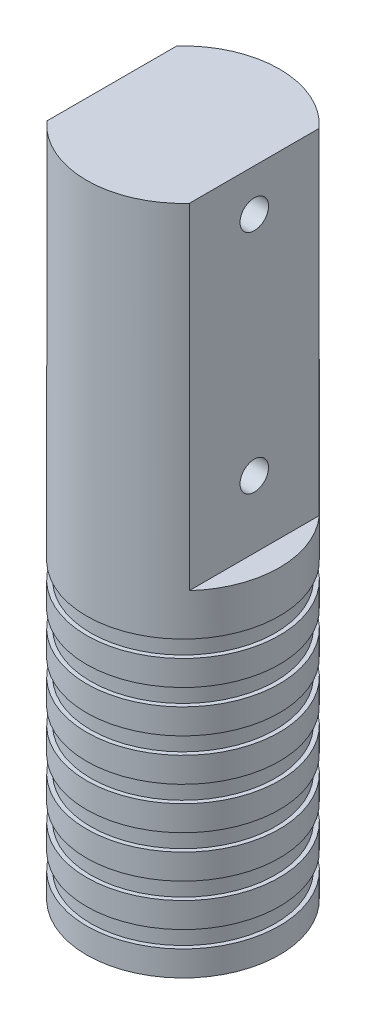
SolidWorks part; units mm, degrees
ref_plane "Front Plane" through (0, 0, 0) normal (0, 0, 1) x (1, 0, 0)
ref_plane "Top Plane" through (0, 0, 0) normal (0, 1, 0) x (1, 0, 0)
ref_plane "Right Plane" through (0, 0, 0) normal (1, 0, 0) x (0, 0, -1)
sketch "Sketch2" plane through (0, 0, 0) normal (0, 0, 1) x (1, 0, 0)
  line L0 (-11.5, 0) -> (11.5, 0)
  line L1 (11.5, 0) -> (11.5, -40)
  line L2 (11.5, -40) -> (0, -40)
  line L4 (0, 0) -> (0, -40)
  line L6 (-11.5, -40) -> (0, -40)
  line L7 (-11.5, 0) -> (-11.5, -40)
  point P3 (0, -40)
  point P4 (0, 0)
  point P8 (0.2527, -40)
  dimension "D1" = 23
  dimension "D4" = 40
revolve "Revolve1" add sketch "Sketch2" angle 360 about L4 region at (-5.75, -20, 0)
sketch "Sketch3" plane through (0, 0, 0) normal (0, 0, 1) x (1, 0, 0)
  line L0 (-11.5, -40) -> (11.5, -40) construction
  line L1 (-11.5, -40) -> (11.5, -40)
  line L2 (11.5, -40) -> (11.5, -37)
  line L3 (11.5, -40) -> (11.5, 0) construction
  line L4 (11.5, -37) -> (11, -37)
  line L5 (11, -37) -> (11, -35)
  line L6 (11, -35) -> (11.5, -35)
  line L7 (11.5, -37) -> (11.5, -35)
  dimension "D1" = 2
  dimension "D2" = 0.5
  dimension "D3" = 3
revolve "Cut-Revolve1" cut sketch "Sketch3" angle 360 about L4
pattern_linear "LPattern1" count 7 spacing 5 along (0, 1, 0) of "Cut-Revolve1"
sketch "Sketch4" plane through (0, -40, 0) normal (0, -1, 0) x (1, 0, 0)
  point P0 (0, 0)
sketch "Sketch6" plane through (0, 0, 0) normal (0, 1, 0) x (1, 0, 0)
  line L0 (-8.5, 7.746) -> (-8.5, -7.746)
  line L2 (0, 0) -> (0, 11.5) construction
  line L3 (8.5, 7.746) -> (8.5, -7.746)
  line L4 (0, 0) -> (-8.5, 0) construction
  line L5 (-8.5, 1.5) -> (0, 1.5) construction
  arc A0 (8.5, 7.746) -> (-8.5, 7.746) centre (0, 0) ccw
  circle A1 centre (0, 0) radius 11.5 construction
  arc A2 (8.5, -7.746) -> (-8.5, -7.746) centre (0, 0) cw
  point P7 (-11.5, 0)
  point P8 (0, 0)
  point P15 (0, 0)
  point P16 (8.3695, 7.8868)
  dimension "D1" = 3
  dimension "D2" = 1.5
extrude "Boss-Extrude1" add sketch "Sketch6" along normal blind 40
hole_wizard "Ø15.0 (15) Diameter Hole1" positions "Sketch4" profile "Sketch5" hole size "Ø15.0" standard "ANSI Metric"
sketch "Sketch5" plane through (0, -40, 0) normal (1, 0, 0) x (0, 0, -1)
  line L0 (0, 0) -> (0, 44.5065)
  line L1 (0, 44.5065) -> (7.5, 40)
  line L2 (7.5, 40) -> (7.5, 0)
  line L5 (7.5, 0) -> (0, 0)
  line L10 (0, 44.5065) -> (-7.5, 40) construction
  line L11 (0, -6.35) -> (0, 107.95) construction
  dimension "Hole Dia." = 15
  dimension "Hole Depth" = 40
  dimension "Drill Angle" = 118
sketch "Sketch8" plane through (8.5, 0, 0) normal (1, 0, 0) x (0, 0, -1)
  line L2 (0, 8) -> (0, 35) construction
  line L3 (7.746, 0) -> (-7.746, 0) construction
  circle A0 centre (0, 8) radius 1.5 construction
  point P0 (0, 8)
  point P1 (0, 35)
  dimension "D1" = 3
  dimension "D2" = 8
  dimension "D3" = 27
hole_wizard "M3 Clearance Hole1" positions "Sketch8" profile "Sketch14" hole size "M3" standard "ANSI Metric" end condition through all
sketch "Sketch14" plane through (8.5, 8, 0) normal (0, 1, 0) x (0, 0, -1)
  line L0 (0, 0) -> (0, 20)
  line L1 (0, 20) -> (1.7, 20)
  line L2 (1.7, 20) -> (1.7, 0)
  line L5 (1.7, 0) -> (0, 0)
  line L11 (0, -6.35) -> (0, 107.95) construction
  point P3 (0, 0)
  dimension "Thru Hole Dia." = 3.4
  dimension "Thru Hole Depth" = 20
